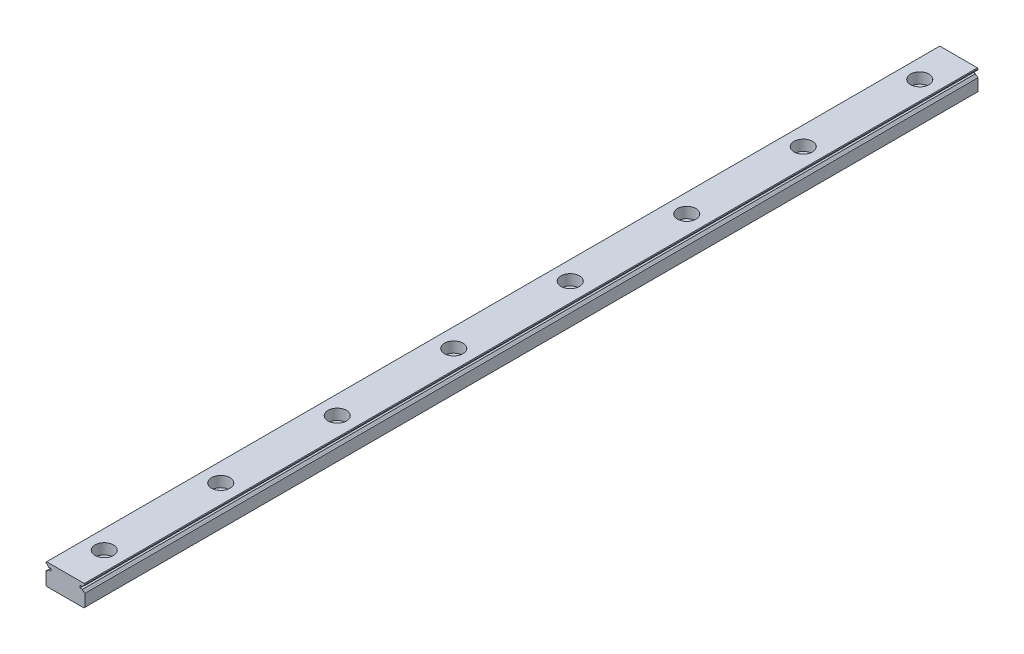
SolidWorks part; units mm, degrees
ref_plane "Front Plane" through (0, 0, 0) normal (0, 0, 1) x (1, 0, 0)
ref_plane "Top Plane" through (0, 0, 0) normal (0, 1, 0) x (1, 0, 0)
ref_plane "Right Plane" through (0, 0, 0) normal (1, 0, 0) x (0, 0, -1)
ref_plane "Plane1" through (0, 0, 0) normal (0, 0, 1) x (1, 0, 0)
sketch "Sketch1" plane through (0, 0, 0) normal (0, 0, 1) x (1, 0, 0)
  line L0 (-10, 6.7761) -> (-10, 0.5)
  line L1 (-10, 0.5) -> (-9.5, 0)
  line L2 (-9.5, 0) -> (9.5, 0)
  line L3 (9.5, 0) -> (10, 0.5)
  line L4 (10, 0.5) -> (10, 6.7761)
  line L5 (10, 6.7761) -> (9.44, 7.0994)
  line L6 (8.7177, 7.9) -> (7.5, 7.9)
  line L7 (7.5, 7.9) -> (7.5, 9.1)
  line L8 (7.5, 9.1) -> (8.7177, 9.1)
  line L9 (9.44, 9.9006) -> (10, 10.2238)
  line L10 (10, 10.2238) -> (10, 10.7)
  line L11 (10, 10.7) -> (9.7, 11)
  line L12 (9.7, 11) -> (-9.7, 11)
  line L13 (-9.7, 11) -> (-10, 10.7)
  line L14 (-10, 10.7) -> (-10, 10.2238)
  line L15 (-10, 10.2238) -> (-9.44, 9.9006)
  line L16 (-8.7177, 9.1) -> (-7.5, 9.1)
  line L17 (-7.5, 9.1) -> (-7.5, 7.9)
  line L18 (-7.5, 7.9) -> (-8.7177, 7.9)
  line L19 (-9.44, 7.0994) -> (-10, 6.7761)
  arc A0 (9.44, 7.0994) -> (8.7177, 7.9) centre (10.315, 8.615) cw
  arc A1 (8.7177, 9.1) -> (9.44, 9.9006) centre (10.315, 8.385) cw
  arc A2 (-9.44, 9.9006) -> (-8.7177, 9.1) centre (-10.315, 8.385) cw
  arc A3 (-8.7177, 7.9) -> (-9.44, 7.0994) centre (-10.315, 8.615) cw
extrude "Boss-Extrude1" add sketch "Sketch1" against normal blind 230 and the other way blind 230
ref_plane "Plane2" through (0, 0, 0) normal (1, 0, 0) x (0, 0, -1)
sketch "Sketch2" plane through (0, 0, 0) normal (1, 0, 0) x (0, 0, -1)
  line L0 (210, 11) -> (214.75, 11)
  line L1 (214.75, 11) -> (214.75, 5.5)
  line L2 (214.75, 5.5) -> (213, 5.5)
  line L3 (213, 5.5) -> (213, 0)
  line L4 (213, 0) -> (210, 0)
  line L5 (210, 0) -> (210, 11)
  line L6 (210, 0) -> (210, 11) construction
revolve "Cut-Revolve1" cut sketch "Sketch2" angle 360 about L6 reverse direction yes
ref_plane "Plane3" through (0, 0, 0) normal (1, 0, 0) x (0, 0, -1)
sketch "Sketch3" plane through (0, 0, 0) normal (1, 0, 0) x (0, 0, -1)
  line L0 (150, 11) -> (154.75, 11)
  line L1 (154.75, 11) -> (154.75, 5.5)
  line L2 (154.75, 5.5) -> (153, 5.5)
  line L3 (153, 5.5) -> (153, 0)
  line L4 (153, 0) -> (150, 0)
  line L5 (150, 0) -> (150, 11)
  line L6 (150, 0) -> (150, 11) construction
revolve "Cut-Revolve2" cut sketch "Sketch3" angle 360 about L6 reverse direction yes
ref_plane "Plane4" through (0, 0, 0) normal (1, 0, 0) x (0, 0, -1)
sketch "Sketch4" plane through (0, 0, 0) normal (1, 0, 0) x (0, 0, -1)
  line L0 (90, 11) -> (94.75, 11)
  line L1 (94.75, 11) -> (94.75, 5.5)
  line L2 (94.75, 5.5) -> (93, 5.5)
  line L3 (93, 5.5) -> (93, 0)
  line L4 (93, 0) -> (90, 0)
  line L5 (90, 0) -> (90, 11)
  line L6 (90, 0) -> (90, 11) construction
revolve "Cut-Revolve3" cut sketch "Sketch4" angle 360 about L6 reverse direction yes
ref_plane "Plane5" through (0, 0, 0) normal (1, 0, 0) x (0, 0, -1)
sketch "Sketch5" plane through (0, 0, 0) normal (1, 0, 0) x (0, 0, -1)
  line L0 (30, 11) -> (34.75, 11)
  line L1 (34.75, 11) -> (34.75, 5.5)
  line L2 (34.75, 5.5) -> (33, 5.5)
  line L3 (33, 5.5) -> (33, 0)
  line L4 (33, 0) -> (30, 0)
  line L5 (30, 0) -> (30, 11)
  line L6 (30, 0) -> (30, 11) construction
revolve "Cut-Revolve4" cut sketch "Sketch5" angle 360 about L6 reverse direction yes
ref_plane "Plane6" through (0, 0, 0) normal (1, 0, 0) x (0, 0, -1)
sketch "Sketch6" plane through (0, 0, 0) normal (1, 0, 0) x (0, 0, -1)
  line L0 (-30, 11) -> (-25.25, 11)
  line L1 (-25.25, 11) -> (-25.25, 5.5)
  line L2 (-25.25, 5.5) -> (-27, 5.5)
  line L3 (-27, 5.5) -> (-27, 0)
  line L4 (-27, 0) -> (-30, 0)
  line L5 (-30, 0) -> (-30, 11)
  line L6 (-30, 0) -> (-30, 11) construction
revolve "Cut-Revolve5" cut sketch "Sketch6" angle 360 about L6 reverse direction yes
ref_plane "Plane7" through (0, 0, 0) normal (1, 0, 0) x (0, 0, -1)
sketch "Sketch7" plane through (0, 0, 0) normal (1, 0, 0) x (0, 0, -1)
  line L0 (-90, 11) -> (-85.25, 11)
  line L1 (-85.25, 11) -> (-85.25, 5.5)
  line L2 (-85.25, 5.5) -> (-87, 5.5)
  line L3 (-87, 5.5) -> (-87, 0)
  line L4 (-87, 0) -> (-90, 0)
  line L5 (-90, 0) -> (-90, 11)
  line L6 (-90, 0) -> (-90, 11) construction
revolve "Cut-Revolve6" cut sketch "Sketch7" angle 360 about L6 reverse direction yes
ref_plane "Plane8" through (0, 0, 0) normal (1, 0, 0) x (0, 0, -1)
sketch "Sketch8" plane through (0, 0, 0) normal (1, 0, 0) x (0, 0, -1)
  line L0 (-150, 11) -> (-145.25, 11)
  line L1 (-145.25, 11) -> (-145.25, 5.5)
  line L2 (-145.25, 5.5) -> (-147, 5.5)
  line L3 (-147, 5.5) -> (-147, 0)
  line L4 (-147, 0) -> (-150, 0)
  line L5 (-150, 0) -> (-150, 11)
  line L6 (-150, 0) -> (-150, 11) construction
revolve "Cut-Revolve7" cut sketch "Sketch8" angle 360 about L6 reverse direction yes
ref_plane "Plane9" through (0, 0, 0) normal (1, 0, 0) x (0, 0, -1)
sketch "Sketch9" plane through (0, 0, 0) normal (1, 0, 0) x (0, 0, -1)
  line L0 (-210, 11) -> (-205.25, 11)
  line L1 (-205.25, 11) -> (-205.25, 5.5)
  line L2 (-205.25, 5.5) -> (-207, 5.5)
  line L3 (-207, 5.5) -> (-207, 0)
  line L4 (-207, 0) -> (-210, 0)
  line L5 (-210, 0) -> (-210, 11)
  line L6 (-210, 0) -> (-210, 11) construction
revolve "Cut-Revolve8" cut sketch "Sketch9" angle 360 about L6 reverse direction yes
